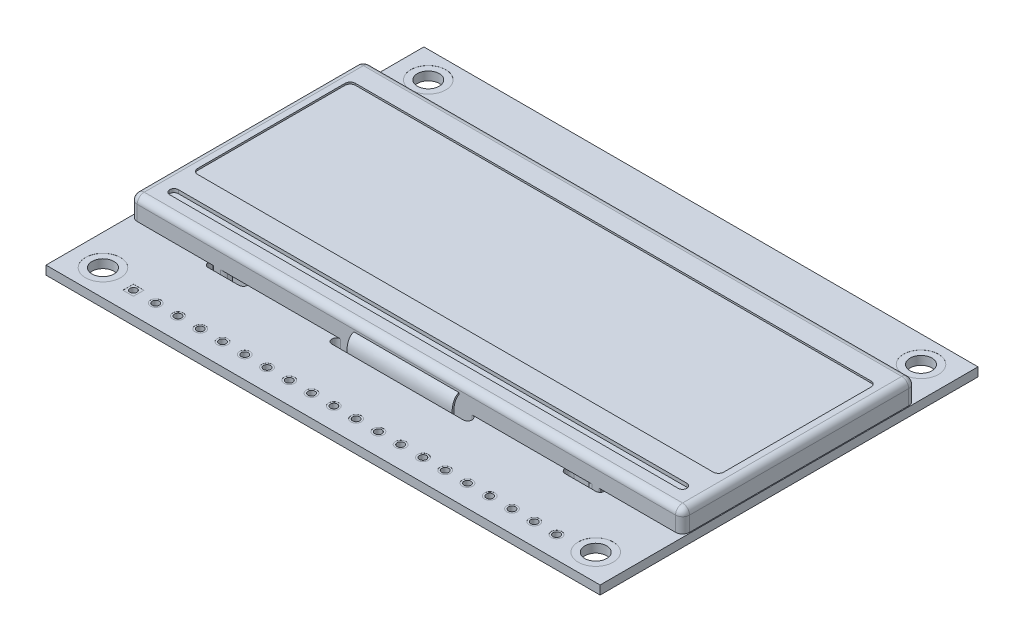
SolidWorks part; units mm, degrees
ref_plane "Front" through (0, 0, 0) normal (0, 0, 1) x (1, 0, 0)
ref_plane "Top" through (0, 0, 0) normal (0, 1, 0) x (1, 0, 0)
ref_plane "Right" through (0, 0, 0) normal (1, 0, 0) x (0, 0, -1)
sketch "Sketch1" plane through (0, 0, 0) normal (0, 1, 0) x (1, 0, 0)
  line L1 (0, 0) -> (63.2, 0)
  line L2 (0, 0) -> (0, 43.1)
  line L3 (0, 43.1) -> (63.2, 43.1)
  line L4 (63.2, 0) -> (63.2, 43.1)
  dimension "D1" = 63.2
  dimension "D2" = 43.1
extrude "Boss-Extrude1" add sketch "Sketch1" along normal blind 1
sketch "Sketch2" plane through (0, 1, 0) normal (0, 1, 0) x (1, 0, 0)
  line L0 (63.2, 43.1) -> (0, 43.1) construction
  line L1 (0, 0) -> (63.2, 0) construction
  line L2 (0, 43.1) -> (0, 0) construction
  line L3 (63.2, 0) -> (63.2, 43.1) construction
  circle A0 centre (3.5, 40.1) radius 1.25
  circle A1 centre (59.7, 40.1) radius 1.25
  circle A2 centre (59.7, 3) radius 1.25
  circle A3 centre (3.5, 3) radius 1.25
  dimension "D1" = 3
  dimension "D2" = 3
  dimension "D7" = 3.5
  dimension "D8" = 3.5
  dimension "D9" = 2.5
  dimension "D10" = 2.5
  dimension "D11" = 2.5
  dimension "D12" = 2.5
  dimension "D3" = 3
  dimension "D4" = 3
  dimension "D5" = 3.5
  dimension "D6" = 3.5
extrude "Cut-Extrude1" cut sketch "Sketch2" against normal up to next
sketch "Sketch3" plane through (0, 1, 0) normal (0, 1, 0) x (1, 0, 0)
  line L0 (0, 43.1) -> (0, 0) construction
  line L1 (0, 0) -> (63.2, 0) construction
  circle A0 centre (7.47, 2.5) radius 0.4
  circle A1 centre (10.01, 2.5) radius 0.4
  circle A2 centre (12.55, 2.5) radius 0.4
  circle A3 centre (15.09, 2.5) radius 0.4
  circle A4 centre (17.63, 2.5) radius 0.4
  circle A5 centre (20.17, 2.5) radius 0.4
  circle A6 centre (22.71, 2.5) radius 0.4
  circle A7 centre (25.25, 2.5) radius 0.4
  circle A8 centre (27.79, 2.5) radius 0.4
  circle A9 centre (30.33, 2.5) radius 0.4
  circle A10 centre (32.87, 2.5) radius 0.4
  circle A11 centre (35.41, 2.5) radius 0.4
  circle A12 centre (37.95, 2.5) radius 0.4
  circle A13 centre (40.49, 2.5) radius 0.4
  circle A14 centre (43.03, 2.5) radius 0.4
  circle A15 centre (45.57, 2.5) radius 0.4
  circle A16 centre (48.11, 2.5) radius 0.4
  circle A17 centre (50.65, 2.5) radius 0.4
  circle A18 centre (53.19, 2.5) radius 0.4
  circle A19 centre (55.73, 2.5) radius 0.4
  dimension "D1" = 7.47
  dimension "D2" = 0.8
  dimension "D3" = 2.5
  dimension "D4" = 20
extrude "Cut-Extrude2" cut sketch "Sketch3" against normal up to next
sketch "Sketch4" plane through (0, 1, 0) normal (0, 1, 0) x (1, 0, 0)
  line L0 (63.2, 43.1) -> (0, 43.1) construction
  line L1 (0.1, 36.1) -> (63.1, 36.1)
  line L2 (0.1, 36.1) -> (0.1, 9.5)
  line L3 (0.1, 9.5) -> (63.1, 9.5)
  line L4 (63.1, 36.1) -> (63.1, 9.5)
  line L5 (0, 43.1) -> (0, 0) construction
  line L6 (63.2, 0) -> (63.2, 43.1) construction
  dimension "D1" = 7
  dimension "D2" = 26.6
  dimension "D3" = 0.1
  dimension "D4" = 0.1
extrude "Boss-Extrude2" add sketch "Sketch4" along normal blind 2.5
sketch "Sketch5" plane through (0, 1, 0) normal (0, 1, 0) x (1, 0, 0)
  line L0 (0.1, 9.5) -> (63.1, 9.5) construction
  line L1 (23.6, 9.5) -> (39.6, 9.5)
  line L2 (23.6, 9.5) -> (23.6, 8.5)
  line L3 (23.6, 8.5) -> (39.6, 8.5)
  line L4 (39.6, 9.5) -> (39.6, 8.5)
  line L5 (0, 43.1) -> (0, 0) construction
  dimension "D1" = 16
  dimension "D2" = 1
  dimension "D3" = 23.6
extrude "Cut-Extrude3" cut sketch "Sketch5" against normal up to next
fillet "Fillet1" radius 0.5 4 edges at (39.6, 0.5, -8.5) (39.6, 0.5, -9.5) (23.6, 0.5, -8.5) (23.6, 0.5, -9.5)
sketch "Sketch6" plane through (0, 3.5, 0) normal (0, 1, 0) x (1, 0, 0)
  line L0 (0.1, 36.1) -> (0.1, 9.5) construction
  line L1 (2.2, 33.1) -> (61, 33.1)
  line L2 (1.6, 32.5) -> (1.6, 15.7)
  line L3 (2.2, 15.1) -> (61, 15.1)
  line L4 (61.6, 32.5) -> (61.6, 15.7)
  line L5 (63.1, 36.1) -> (0.1, 36.1) construction
  arc A0 (61, 15.1) -> (61.6, 15.7) centre (61, 15.7) ccw
  arc A1 (61, 33.1) -> (61.6, 32.5) centre (61, 32.5) cw
  arc A2 (1.6, 15.7) -> (2.2, 15.1) centre (2.2, 15.7) ccw
  arc A3 (2.2, 33.1) -> (1.6, 32.5) centre (2.2, 32.5) ccw
  point P12 (61.6, 33.1)
  point P15 (1.6, 15.1)
  point P18 (1.6, 33.1)
  dimension "D5" = 0.6
  dimension "D1" = 60
  dimension "D2" = 1.5
  dimension "D3" = 18
  dimension "D4" = 3
extrude "Cut-Extrude4" cut sketch "Sketch6" against normal blind 0.2
sketch "Sketch7" plane through (0, 3.5, 0) normal (0, 1, 0) x (1, 0, 0)
  line L0 (0.1, 36.1) -> (0.1, 9.5) construction
  line L1 (2.1, 12.5) -> (61.1, 12.5)
  line L2 (2.1, 12.5) -> (2.1, 11.5)
  line L3 (2.1, 11.5) -> (61.1, 11.5)
  line L4 (61.1, 12.5) -> (61.1, 11.5)
  line L5 (63.1, 9.5) -> (63.1, 36.1) construction
  line L6 (0.1, 9.5) -> (63.1, 9.5) construction
  dimension "D1" = 1
  dimension "D2" = 2
  dimension "D3" = 2
  dimension "D4" = 2
extrude "Cut-Extrude5" cut sketch "Sketch7" against normal blind 0.4
fillet "Fillet2" radius 0.5 4 edges at (61.1, 3.3, -11.5) (61.1, 3.3, -12.5) (2.1, 3.3, -11.5) (2.1, 3.3, -12.5)
fillet "Fillet3" radius 0.8 4 edges at (63.1, 2.25, -36.1) (63.1, 2.25, -9.5) (0.1, 2.25, -9.5) (0.1, 2.25, -36.1)
fillet "Fillet4" radius 0.8 8 edges at (0.3343, 3.5, -35.8657) (31.6, 3.5, -36.1) (62.8657, 3.5, -35.8657) (63.1, 3.5, -22.8) (62.8657, 3.5, -9.7343) (31.6, 3.5, -9.5) (0.3343, 3.5, -9.7343) (0.1, 3.5, -22.8)
sketch "Sketch8" plane through (0, 0, 0) normal (0, -1, 0) x (1, 0, 0)
  line L0 (24.1, -8.5) -> (39.1, -8.5) construction
  line L1 (54.2, -10) -> (49.7, -10)
  line L2 (54.2, -10) -> (54.2, -9)
  line L3 (54.2, -9) -> (49.7, -9)
  line L4 (49.7, -10) -> (49.7, -9)
  line L5 (13.5, -9) -> (9, -9)
  line L6 (13.5, -9) -> (13.5, -10)
  line L7 (13.5, -10) -> (9, -10)
  line L8 (9, -9) -> (9, -10)
  line L9 (63.2, 0) -> (63.2, -43.1) construction
  line L10 (0, -43.1) -> (0, 0) construction
  line L12 (13.5, -35.6) -> (9, -35.6)
  line L13 (13.5, -35.6) -> (13.5, -36.6)
  line L14 (13.5, -36.6) -> (9, -36.6)
  line L15 (9, -35.6) -> (9, -36.6)
  line L16 (54.2, -35.6) -> (49.7, -35.6)
  line L17 (54.2, -35.6) -> (54.2, -36.6)
  line L18 (54.2, -36.6) -> (49.7, -36.6)
  line L19 (49.7, -35.6) -> (49.7, -36.6)
  dimension "D1" = 1
  dimension "D2" = 1
  dimension "D3" = 0.5
  dimension "D4" = 0.5
  dimension "D5" = 4.5
  dimension "D6" = 4.5
  dimension "D7" = 9
  dimension "D8" = 9
  dimension "D9" = 1
  dimension "D10" = 9
  dimension "D11" = 1
  dimension "D12" = 9
  dimension "D13" = 25.6
  dimension "D14" = 25.6
extrude "Cut-Extrude6" cut sketch "Sketch8" against normal blind 1
fillet "Fillet5" radius 0.5 16 edges at (13.5, 0.5, -9) (13.5, 0.5, -10) (9, 0.5, -10) (9, 0.5, -9) (13.5, 0.5, -35.6) (13.5, 0.5, -36.6) (9, 0.5, -35.6) (9, 0.5, -36.6) (49.7, 0.5, -9) (49.7, 0.5, -10) (54.2, 0.5, -9) (54.2, 0.5, -10) (49.7, 0.5, -35.6) (49.7, 0.5, -36.6) (54.2, 0.5, -35.6) (54.2, 0.5, -36.6)
sketch "Sketch9" plane through (0, 0, 0) normal (0, -1, 0) x (1, 0, 0)
  line L0 (63.2, -43.1) -> (0, -43.1) construction
  line L1 (40.1, -42.1) -> (23.1, -42.1)
  line L2 (40.1, -42.1) -> (40.1, -38.1)
  line L3 (40.1, -38.1) -> (23.1, -38.1)
  line L4 (23.1, -42.1) -> (23.1, -38.1)
  line L5 (63.2, 0) -> (63.2, -43.1) construction
  dimension "D1" = 17
  dimension "D2" = 4
  dimension "D3" = 1
  dimension "D4" = 23.1
extrude "Boss-Extrude3" add sketch "Sketch9" along normal blind 2
sketch "Sketch10" plane through (0, 0, -42.1) normal (0, 0, -1) x (-1, 0, 0)
  line L0 (-23.1, -2) -> (-40.1, -2) construction
  line L1 (-25.1, -2) -> (-38.1, -2)
  line L2 (-25.1, -2) -> (-25.1, 0)
  line L3 (-25.1, 0) -> (-38.1, 0)
  line L4 (-38.1, -2) -> (-38.1, 0)
  line L5 (-23.1, 0) -> (-40.1, 0) construction
  line L6 (-23.1, -2) -> (-23.1, 0) construction
  line L7 (-40.1, -2) -> (-40.1, 0) construction
  dimension "D1" = 2
  dimension "D2" = 2
extrude "Cut-Extrude7" cut sketch "Sketch10" against normal blind 0.4
ref_plane "Plane1" through (31.6, 0, 0) normal (1, 0, 0) x (0, 0, -1)
sketch "Sketch12" plane through (0, 0, -38.1) normal (0, 0, 1) x (1, 0, 0)
  line L0 (23.1, -2) -> (23.1, 0) construction
  line L1 (37.6, -1.1) -> (25.6, -1.1)
  line L2 (37.6, -1.1) -> (37.6, -0.9)
  line L3 (37.6, -0.9) -> (25.6, -0.9)
  line L4 (25.6, -1.1) -> (25.6, -0.9)
  line L5 (40.1, 0) -> (23.1, 0) construction
  dimension "D1" = 12
  dimension "D2" = 2.5
  dimension "D3" = 0.2
  dimension "D4" = 0.9
sketch "Sketch13" plane through (31.6, 0, 0) normal (1, 0, 0) x (0, 0, -1)
  line L2 (42.1, -2) -> (42.1, 0) construction
  spline S0 degree 3 poles (38.1, -0.9829) (31.6934, -1.1952) (28.2414, -1.4022) (7.9165, -4.9574) (8.8545, 2.1438) (9.5386, 2.3503) knots 0 0 0 0 0.344257 0.890735 1 1 1 1
  dimension "D1" = 4
sweep "Sweep2" add profiles "Sketch12" path "Sketch13"
sketch "Sketch14" plane through (0, 1, 0) normal (0, 1, 0) x (1, 0, 0)
  circle A0 centre (3.5, 40.1) radius 2
  circle A1 centre (59.7, 40.1) radius 2
  circle A2 centre (59.7, 3) radius 2
  circle A3 centre (3.5, 3) radius 2
  dimension "D1" = 4
  dimension "D2" = 4
  dimension "D3" = 4
  dimension "D4" = 4
extrude "Cut-Extrude8" cut sketch "Sketch14" against normal blind 0.01
sketch "Sketch15" plane through (0, 1, 0) normal (0, 1, 0) x (1, 0, 0)
  line L1 (6.87, 3.1) -> (8.07, 3.1)
  line L2 (6.87, 3.1) -> (6.87, 1.9)
  line L3 (6.87, 1.9) -> (8.07, 1.9)
  line L4 (8.07, 3.1) -> (8.07, 1.9)
  circle A0 centre (7.47, 2.5) radius 0.4 construction
  dimension "D1" = 0.6
  dimension "D2" = 0.6
  dimension "D3" = 0.6
  dimension "D4" = 0.6
extrude "Cut-Extrude9" cut sketch "Sketch15" against normal blind 0.01
sketch "Sketch16" plane through (0, 1, 0) normal (0, 1, 0) x (1, 0, 0)
  circle A0 centre (10.01, 2.5) radius 0.6
  circle A1 centre (12.55, 2.5) radius 0.6
  circle A2 centre (15.09, 2.5) radius 0.6
  circle A3 centre (17.63, 2.5) radius 0.6
  circle A4 centre (20.17, 2.5) radius 0.6
  circle A5 centre (22.71, 2.5) radius 0.6
  circle A6 centre (25.25, 2.5) radius 0.6
  circle A7 centre (27.79, 2.5) radius 0.6
  circle A8 centre (30.33, 2.5) radius 0.6
  circle A9 centre (32.87, 2.5) radius 0.6
  circle A10 centre (35.41, 2.5) radius 0.6
  circle A11 centre (37.95, 2.5) radius 0.6
  circle A12 centre (40.49, 2.5) radius 0.6
  circle A13 centre (43.03, 2.5) radius 0.6
  circle A14 centre (45.57, 2.5) radius 0.6
  circle A15 centre (48.11, 2.5) radius 0.6
  circle A16 centre (50.65, 2.5) radius 0.6
  circle A17 centre (53.19, 2.5) radius 0.6
  circle A18 centre (55.73, 2.5) radius 0.6
  dimension "D1" = 1.2
  dimension "D2" = 19
extrude "Cut-Extrude10" cut sketch "Sketch16" against normal blind 0.01
sketch "Sketch17" plane through (0, 0, 0) normal (0, -1, 0) x (1, 0, 0)
  circle A0 centre (59.7, -40.1) radius 2
  circle A1 centre (3.5, -40.1) radius 2
  circle A2 centre (3.5, -3) radius 2
  circle A3 centre (59.7, -3) radius 2
  dimension "D1" = 4
  dimension "D2" = 4
  dimension "D3" = 4
  dimension "D4" = 4
extrude "Cut-Extrude11" cut sketch "Sketch17" against normal blind 0.01
sketch "Sketch18" plane through (0, 1, 0) normal (0, -1, 0) x (1, 0, 0)
  line L0 (54.2, -36.1) -> (49.7, -36.1) construction
  line L1 (53.7, -35.6) -> (51.95, -35.6)
  line L2 (53.7, -35.6) -> (53.7, -36.1)
  line L3 (53.7, -36.1) -> (51.95, -36.1)
  line L4 (51.95, -35.6) -> (51.95, -36.1)
  line L5 (13.5, -36.1) -> (9, -36.1) construction
  line L6 (9.5, -35.6) -> (11.25, -35.6)
  line L7 (9.5, -35.6) -> (9.5, -36.1)
  line L8 (9.5, -36.1) -> (11.25, -36.1)
  line L9 (11.25, -35.6) -> (11.25, -36.1)
  line L10 (49.7, -9.5) -> (54.2, -9.5) construction
  line L11 (53.7, -10) -> (51.95, -10)
  line L12 (53.7, -10) -> (53.7, -9.5)
  line L13 (53.7, -9.5) -> (51.95, -9.5)
  line L14 (51.95, -10) -> (51.95, -9.5)
  line L15 (9, -9.5) -> (13.5, -9.5) construction
  line L16 (9.5, -10) -> (11.25, -10)
  line L17 (9.5, -10) -> (9.5, -9.5)
  line L18 (9.5, -9.5) -> (11.25, -9.5)
  line L19 (11.25, -10) -> (11.25, -9.5)
  arc A0 (54.2, -36.1) -> (53.7, -35.6) centre (53.7, -36.1) ccw construction
  arc A1 (9.5, -35.6) -> (9, -36.1) centre (9.5, -36.1) ccw construction
extrude "Boss-Extrude4" add sketch "Sketch18" along normal blind 1
chamfer "Chamfer1" distance 0.5 angle 45 4 edges at (11.25, 0.5, -9.5) (11.25, 0.5, -36.1) (51.95, 0.5, -36.1) (51.95, 0.5, -9.5)
sketch "Sketch19" plane through (0, 0, 0) normal (0, -1, 0) x (-1, 0, 0)
  line L0 (-9.5, 9.5) -> (-10.75, 9.5)
  line L1 (-10.75, 9.5) -> (-12.5178, 11.2678)
  line L2 (-12.5178, 11.2678) -> (-12.1642, 11.6213)
  line L3 (-12.1642, 11.6213) -> (-10.5429, 10)
  line L4 (-10.5429, 10) -> (-9.5, 10)
  line L5 (-9.5, 10) -> (-9.5, 9.5)
  line L6 (-53.7, 9.5) -> (-52.45, 9.5)
  line L7 (-52.45, 9.5) -> (-50.6822, 11.2678)
  line L8 (-50.6822, 11.2678) -> (-51.0358, 11.6213)
  line L9 (-51.0358, 11.6213) -> (-52.6571, 10)
  line L10 (-52.6571, 10) -> (-53.7, 10)
  line L11 (-53.7, 10) -> (-53.7, 9.5)
  line L12 (-9.5, 36.1) -> (-10.75, 36.1)
  line L13 (-10.75, 36.1) -> (-12.5178, 34.3322)
  line L14 (-12.5178, 34.3322) -> (-12.1642, 33.9787)
  line L15 (-12.1642, 33.9787) -> (-10.5429, 35.6)
  line L16 (-10.5429, 35.6) -> (-9.5, 35.6)
  line L17 (-9.5, 35.6) -> (-9.5, 36.1)
  line L18 (-53.7, 36.1) -> (-52.45, 36.1)
  line L19 (-52.45, 36.1) -> (-50.6822, 34.3322)
  line L20 (-50.6822, 34.3322) -> (-51.0358, 33.9787)
  line L21 (-51.0358, 33.9787) -> (-52.6571, 35.6)
  line L22 (-52.6571, 35.6) -> (-53.7, 35.6)
  line L23 (-53.7, 35.6) -> (-53.7, 36.1)
  dimension "D1" = 2.5
  dimension "D2" = 0.5
  dimension "D3" = 135
  dimension "D4" = 90
  dimension "D5" = 135
  dimension "D6" = 90
  dimension "D7" = 2.5
  dimension "D8" = 135
  dimension "D9" = 90
  dimension "D10" = 0.5
  dimension "D11" = 2.5
  dimension "D12" = 0.5
  dimension "D13" = 2.5
  dimension "D14" = 0.5
  dimension "D15" = 135
  dimension "D16" = 135
extrude "Boss-Extrude5" add sketch "Sketch19" along normal blind 1.2
fillet "Fillet6" radius 0.8 8 edges at (10.5429, -0.6, -35.6) (10.75, -0.1, -36.1) (52.6571, -0.6, -35.6) (52.45, -0.1, -36.1) (52.6571, -0.6, -10) (52.45, -0.1, -9.5) (10.75, -0.1, -9.5) (10.5429, -0.6, -10)
fillet "Fillet7" radius 0.1 16 edges at (51.0358, -0.6, -11.6213) (50.6822, -0.6, -11.2678) (53.7, -0.1, -9.5) (53.7, -0.6, -10) (51.0358, -0.6, -33.9787) (50.6822, -0.6, -34.3322) (53.7, -0.6, -35.6) (53.7, -0.1, -36.1) (12.5178, -0.6, -34.3322) (12.1642, -0.6, -33.9787) (9.5, -0.1, -36.1) (9.5, -0.6, -35.6) (9.5, -0.6, -10) (9.5, -0.1, -9.5) (12.1642, -0.6, -11.6213) (12.5178, -0.6, -11.2678)
sketch "Sketch20" plane through (0, 0, 0) normal (0, -1, 0) x (1, 0, 0)
  line L1 (8.07, -3.1) -> (6.87, -3.1)
  line L2 (8.07, -3.1) -> (8.07, -1.9)
  line L3 (8.07, -1.9) -> (6.87, -1.9)
  line L4 (6.87, -3.1) -> (6.87, -1.9)
  circle A0 centre (7.47, -2.5) radius 0.4 construction
  dimension "D1" = 0.6
  dimension "D2" = 0.6
  dimension "D3" = 0.6
  dimension "D4" = 0.6
extrude "Cut-Extrude12" cut sketch "Sketch20" against normal blind 0.01
sketch "Sketch23" plane through (0, 0, 0) normal (0, -1, 0) x (1, 0, 0)
  circle A0 centre (10.01, -2.5) radius 0.6
  circle A1 centre (12.55, -2.5) radius 0.6
  circle A2 centre (15.09, -2.5) radius 0.6
  circle A3 centre (17.63, -2.5) radius 0.6
  circle A4 centre (20.17, -2.5) radius 0.6
  circle A5 centre (22.71, -2.5) radius 0.6
  circle A6 centre (25.25, -2.5) radius 0.6
  circle A7 centre (27.79, -2.5) radius 0.6
  circle A8 centre (30.33, -2.5) radius 0.6
  circle A9 centre (32.87, -2.5) radius 0.6
  circle A10 centre (35.41, -2.5) radius 0.6
  circle A11 centre (37.95, -2.5) radius 0.6
  circle A12 centre (40.49, -2.5) radius 0.6
  circle A13 centre (43.03, -2.5) radius 0.6
  circle A14 centre (45.57, -2.5) radius 0.6
  circle A15 centre (48.11, -2.5) radius 0.6
  circle A16 centre (50.65, -2.5) radius 0.6
  circle A17 centre (53.19, -2.5) radius 0.6
  circle A18 centre (55.73, -2.5) radius 0.6
  dimension "D1" = 1.2
  dimension "D2" = 19
extrude "Cut-Extrude16" cut sketch "Sketch23" against normal blind 0.01
